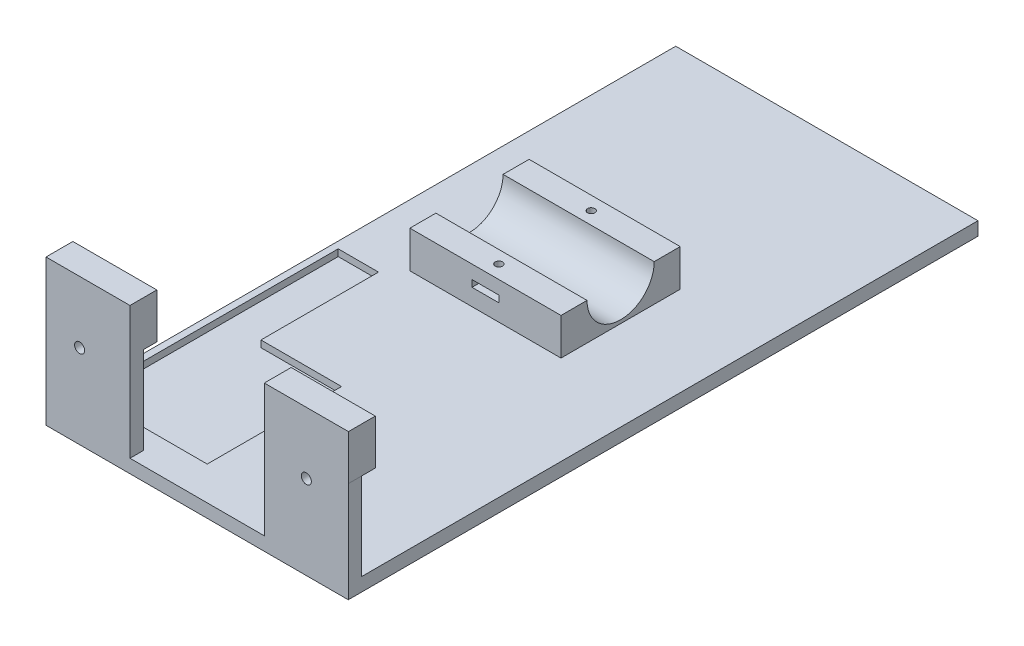
SolidWorks part; units mm, degrees
note: The reader was unsure of these and kept them because the rebuilt part matched: shared geometry of "Superficie_Deitada<4>", "Superficie_Deitada<5>", "Superficie_Deitada<6>", "Superficie_Deitada<7>".
ref_plane "Front Plane" through (0, 0, 0) normal (0, 0, 1) x (1, 0, 0)
ref_plane "Top Plane" through (0, 0, 0) normal (0, 1, 0) x (1, 0, 0)
ref_plane "Right Plane" through (0, 0, 0) normal (1, 0, 0) x (0, 0, -1)
sketch "Superficie_Deitada" plane through (0, 0, 0) normal (0, 1, 0) x (1, 0, 0)
  line L0 (0, 49.4338) -> (0, -7.5662) construction
  line L1 (-45, -133.0662) -> (45, -133.0662)
  line L2 (-45, -133.0662) -> (-45, 54.4338)
  line L3 (-45, 54.4338) -> (45, 54.4338)
  line L4 (45, -133.0662) -> (45, 54.4338)
  line L5 (-45, -125.0662) -> (45, -125.0662)
  line L6 (-45, -48.0662) -> (-45, -123.0662)
  line L7 (-45, 49.4338) -> (45, 49.4338) construction
  line L8 (-45, -7.5662) -> (45, -7.5662) construction
  line L9 (0, -7.5662) -> (0, -15.5662) construction
  line L10 (-26.6609, -35.0662) -> (-26.6609, -15.5662)
  line L11 (-26.6609, -35.0662) -> (18.3391, -35.0662)
  line L12 (-26.6609, -15.5662) -> (18.3391, -15.5662)
  line L13 (18.3391, -35.0662) -> (18.3391, -15.5662)
  line L14 (-26.6609, -35.0662) -> (18.3391, -15.5662) construction
  line L15 (-26.6609, -15.5662) -> (18.3391, -35.0662) construction
  line L16 (0, 49.4338) -> (0, 54.4338) construction
  line L17 (-26.6609, -15.5662) -> (18.3391, -15.5662)
  line L18 (-26.6609, -15.5662) -> (-26.6609, -7.5662)
  line L19 (-26.6609, -7.5662) -> (18.3391, -7.5662)
  line L20 (18.3391, -15.5662) -> (18.3391, -7.5662)
  line L21 (-26.6609, -35.0662) -> (18.3391, -35.0662)
  line L22 (-26.6609, -35.0662) -> (-26.6609, -43.0662)
  line L23 (-26.6609, -43.0662) -> (18.3391, -43.0662)
  line L24 (18.3391, -35.0662) -> (18.3391, -43.0662)
  line L25 (-43, -48.0662) -> (-31, -48.0662)
  line L26 (-43, -123.0662) -> (-31, -123.0662)
  line L27 (-31, -48.0662) -> (-31, -123.0662)
  line L28 (-43, -48.0662) -> (-31, -123.0662) construction
  line L29 (-43, -123.0662) -> (-31, -48.0662) construction
  line L30 (-39, -123.0662) -> (-39, -133.0662) construction
  line L31 (-45, -123.0662) -> (45, -123.0662) construction
  line L32 (-43, -123.0662) -> (-7, -123.0662)
  line L33 (-45, -123.0662) -> (-45, -83.0662)
  line L34 (-43, -83.0662) -> (-7, -83.0662)
  line L35 (-7, -123.0662) -> (-7, -83.0662)
  line L36 (-18, -83.0662) -> (-18, -87.0662) construction
  line L37 (-18, -87.0662) -> (-43, -87.0662) construction
  line L38 (-18, -87.0662) -> (-12, -87.0662) construction
  line L39 (-18, -87.0662) -> (-18, -93.0662) construction
  line L40 (-12, -87.0662) -> (-12, -93.0662) construction
  line L41 (-41.6828, -133.0662) -> (-41.6828, -125.0662) construction
  line L42 (-45, -129.0662) -> (-20, -129.0662)
  line L43 (-43, -48.0662) -> (-43, -123.0662)
  line L44 (-20, -129.0662) -> (-20, -133.0662)
  line L45 (45, -129.0662) -> (20, -129.0662)
  line L46 (20, -129.0662) -> (20, -133.0662)
  circle A0 centre (-18, -87.0662) radius 1.1
  circle A1 centre (-18, -93.0662) radius 1.1
  circle A2 centre (-12, -93.0662) radius 1.1
  circle A3 centre (-12, -87.0662) radius 1.1
  point P0 (0, 0)
  point P14 (-4.1609, -25.3162)
  point P29 (-39, -85.5662)
sketch "Superficie_vertical" plane through (0, 0, 0) normal (0, 0, 1) x (1, 0, 0)
  line L0 (-45, 0) -> (45, 0) construction
  line L1 (-45, 0) -> (-25, 0)
  line L2 (-45, 0) -> (-45, 43.4)
  line L3 (-45, 43.4) -> (-25, 43.4)
  line L4 (-25, 0) -> (-25, 43.4)
  line L5 (-25, 43.4) -> (-19.95, 43.4) construction
  line L6 (-45, 0) -> (45, 0)
  line L7 (-45, 0) -> (-45, 72.0659)
  line L8 (-45, 72.0659) -> (45, 72.0659)
  line L9 (45, 0) -> (45, 72.0659)
  line L10 (32.5, 30) -> (32.5, 25) construction
  line L11 (20, 0) -> (20, 30) construction
  line L12 (45, 30) -> (20, 30) construction
  line L13 (-25, 30) -> (-45, 30)
  line L14 (-35, 30) -> (-35, 43.4) construction
  line L15 (-35, 30) -> (-35, 25) construction
  circle A0 centre (32.5, 25) radius 1.5
  circle A1 centre (-35, 25) radius 1.5
  point P22 (0, 0)
  point P23 (0, 0)
extrude "Boss-Extrude1" add sketch "Superficie_Deitada" along normal blind 4 contours L2 L5 L4 L3 L6 L43 L25 L27 L34 L35 L32 L26 L13 L24 L23 L22 L10 L18 L19 L20 | L5 L2 L1 L4
extrude "Boss-Extrude2" add sketch "Superficie_Deitada<4>" along normal blind 15 contours L12 L20 L19 L18 | L11 L13 L12 L10 | L24 L11 L22 L23
sketch "Superficie_Deitada<4>" plane through (0, 0, 0) normal (0, 1, 0) x (1, 0, 0) same geometry as "Superficie_Deitada"
extrude "Boss-Extrude3" add sketch "Superficie_Deitada<5>" along normal blind 2 contours L25 L43 L34 L27 | L32 L35 L34 L27 A3 A2 A1 A0 | L34 L43 L26 L27
sketch "Superficie_Deitada<5>" plane through (0, 0, 0) normal (0, 1, 0) x (1, 0, 0) same geometry as "Superficie_Deitada"
extrude "Boss-Extrude4" add sketch "Superficie_Deitada<6>" along normal blind 30 contours L45 L46 L1 L4
sketch "Superficie_Deitada<6>" plane through (0, 0, 0) normal (0, 1, 0) x (1, 0, 0) same geometry as "Superficie_Deitada"
extrude "Boss-Extrude5" add sketch "Superficie_Deitada<7>" along normal blind 30
sketch "Superficie_Deitada<7>" plane through (0, 0, 0) normal (0, 1, 0) x (1, 0, 0) same geometry as "Superficie_Deitada"
extrude "Cut-Extrude1" cut sketch "Superficie_vertical" along normal blind 200.4 contours A0 | A1
sketch "Sketch4" plane through (-26.6609, 0, 0) normal (-1, 0, 0) x (0, 0, 1)
  line L0 (7.5662, 15) -> (15.5662, 15)
  line L1 (43.0662, 15) -> (7.5662, 15) construction
  line L2 (15.5662, 15) -> (35.0662, 15)
  circle A0 centre (25.3162, 15) radius 10
  line M6 (43.0662, 15) -> (7.5662, 15)
extrude "Cut-Extrude2" cut sketch "Sketch4" against normal blind 200.4 contours A0 M6
sketch "Sketch5" plane through (0, 0, 7.5662) normal (0, 0, -1) x (-1, 0, 0)
  line L0 (4.1609, 11) -> (4.1609, 15) construction
  line L2 (26.6609, 15) -> (-18.3391, 15) construction
  line L6 (0.1609, 10) -> (8.1609, 10)
  line L7 (0.1609, 10) -> (0.1609, 12)
  line L8 (0.1609, 12) -> (8.1609, 12)
  line L9 (8.1609, 10) -> (8.1609, 12)
  line L10 (0.1609, 10) -> (8.1609, 12) construction
  line L11 (0.1609, 12) -> (8.1609, 10) construction
  point P5 (0, 0)
  point P6 (0, 0)
extrude "Cut-Extrude3" cut sketch "Sketch5" against normal blind 8
sketch "Sketch6" plane through (0, 10, 0) normal (0, 1, 0) x (1, 0, 0)
  line L0 (-8.1609, -7.5662) -> (-0.1609, -7.5662) construction
  line L1 (-0.1609, -7.5662) -> (-0.1609, -15.5662) construction
  line L2 (-0.1609, -15.5662) -> (-0.1609, -7.5662) construction
  line L3 (-8.1609, -7.5662) -> (-0.1609, -15.5662) construction
  circle A0 centre (-4.1609, -11.5662) radius 1.1
extrude "Cut-Extrude4" cut sketch "Sketch6" along normal blind 7 and the other way blind 3
sketch "Sketch8" plane through (0, 0, 43.0662) normal (0, 0, 1) x (1, 0, 0)
  line L0 (-26.6609, 15) -> (18.3391, 15) construction
  line L1 (-4.1609, 15) -> (-4.1609, 11) construction
  line L2 (-4.1609, 11) -> (-8.1609, 11) construction
  line L4 (-8.1609, 11) -> (-0.1609, 11)
  line L5 (-8.1609, 11) -> (-8.1609, 9)
  line L6 (-8.1609, 9) -> (-0.1609, 9)
  line L7 (-0.1609, 11) -> (-0.1609, 9)
  point P10 (0, 0)
  point P11 (0, 0)
  point P12 (0, 0)
  point P13 (0, 0)
extrude "Cut-Extrude5" cut sketch "Sketch8" against normal blind 8
sketch "Sketch9" plane through (0, 9, 0) normal (0, 1, 0) x (1, 0, 0)
  line L0 (-8.1609, -43.0662) -> (-0.1609, -43.0662) construction
  line L1 (-0.1609, -43.0662) -> (-0.1609, -35.0662) construction
  line L2 (-0.1609, -35.0662) -> (-0.1609, -43.0662) construction
  line L3 (-0.1609, -35.0662) -> (-8.1609, -43.0662) construction
  circle A0 centre (-4.1609, -39.0662) radius 1.1
extrude "Cut-Extrude6" cut sketch "Sketch9" along normal blind 15 and the other way blind 3
sketch "Sketch11" plane through (0, 30, 0) normal (0, 1, 0) x (1, 0, 0)
  line L1 (20, -133.0662) -> (45.05, -133.0662)
  line L2 (20, -133.0662) -> (20, -125.0662)
  line L3 (20, -125.0662) -> (45.05, -125.0662)
  line L4 (45.05, -133.0662) -> (45.05, -125.0662)
  point P5 (0, 0)
extrude "Boss-Extrude6" add sketch "Sketch11" along normal blind 13.4
sketch "Sketch12" plane through (0, 30, 0) normal (0, 1, 0) x (1, 0, 0)
  line L1 (-45, -133.0662) -> (-20, -133.0662)
  line L2 (-45, -133.0662) -> (-45, -125.0662)
  line L3 (-45, -125.0662) -> (-20, -125.0662)
  line L4 (-20, -133.0662) -> (-20, -125.0662)
  point P5 (0, 0)
extrude "Boss-Extrude7" add sketch "Sketch12" along normal blind 13.4 contours L3 L4 L1 L2
